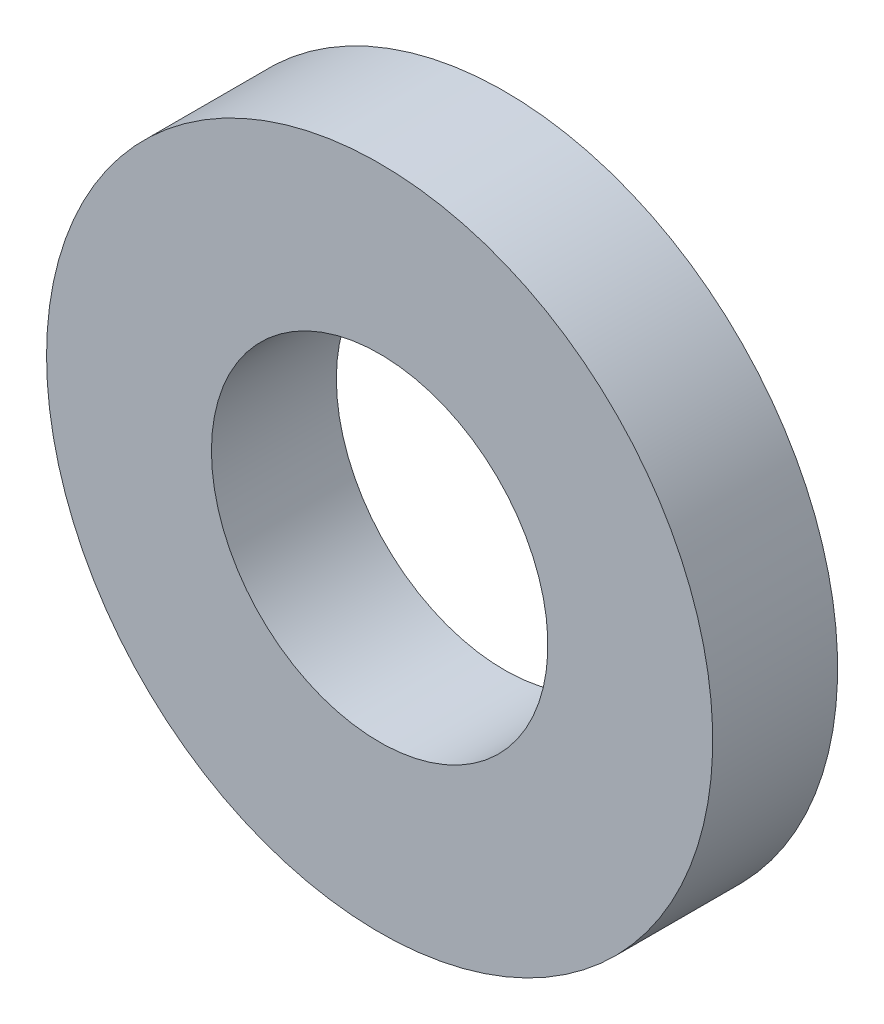
SolidWorks part; units mm, degrees
ref_plane "Front Plane" through (0, 0, 0) normal (0, 0, 1) x (1, 0, 0)
ref_plane "Top Plane" through (0, 0, 0) normal (0, 1, 0) x (1, 0, 0)
ref_plane "Right Plane" through (0, 0, 0) normal (1, 0, 0) x (0, 0, -1)
sketch "Sketch1" plane through (0, 0, 0) normal (0, 0, 1) x (1, 0, 0)
  circle A0 centre (0, 0) radius 12.7
  circle A1 centre (0, 0) radius 6.4135
  dimension "OD" = 25.4
  dimension "ID" = 12.827
extrude "Extrude1" add sketch "Sketch1" along normal mid plane 4.7625
sketch "Sketch2" plane through (0, 0, 0) normal (1, 0, 0) x (0, 0, -1)
  line L0 (-2.3813, -6.4135) -> (2.3812, -6.4135) construction
  line L3 (2.3812, 6.4135) -> (-2.3813, 6.4135) construction
  line L5 (-2.3813, -6.4135) -> (2.3812, -6.4135)
  line L6 (2.3812, 6.4135) -> (-2.3813, 6.4135)
sketch "Sketch4" plane through (0, 0, 2.3813) normal (0, 0, 1) x (1, 0, 0)
  line L0 (0, 0) -> (-4.535, 4.535)
  line L1 (0, -1.7463) -> (0, 1.7463) construction
  circle A0 centre (0, 0) radius 6.4135 construction
  dimension "D1" = 45
